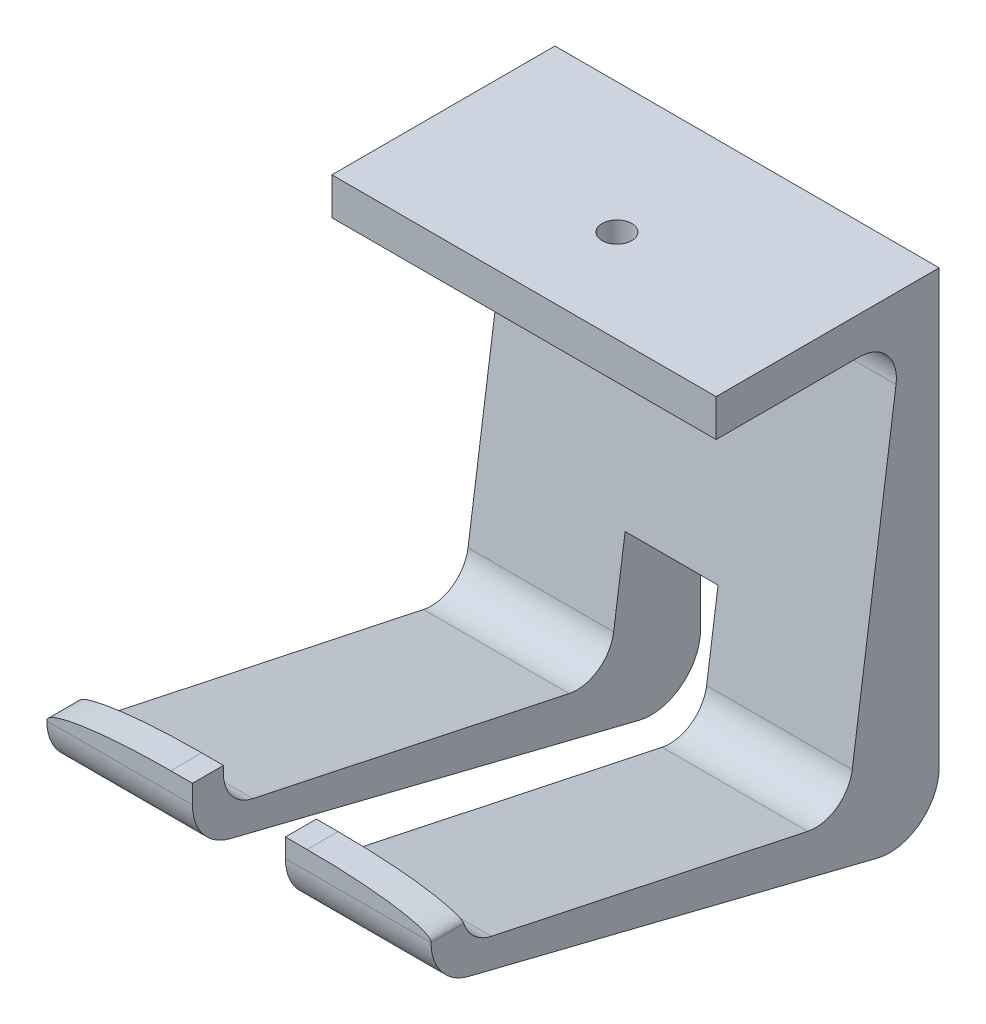
SolidWorks part; units mm, degrees
ref_plane "Front Plane" through (0, 0, 0) normal (0, 0, 1) x (1, 0, 0)
ref_plane "Top Plane" through (0, 0, 0) normal (0, 1, 0) x (1, 0, 0)
ref_plane "Right Plane" through (0, 0, 0) normal (1, 0, 0) x (0, 0, -1)
sketch "Sketch1" plane through (0, 0, 0) normal (1, 0, 0) x (0, 0, -1)
  line L0 (0, 0) -> (23.0978, 0)
  line L1 (29.0394, -6.835) -> (21.9739, -57.1088)
  line L2 (14.7848, -62.1426) -> (-36.2475, -51.2954)
  line L4 (0, 0) -> (0, 6)
  line L5 (0, 6) -> (36, 6)
  line L6 (36, 6) -> (36, -63.7605)
  line L7 (26.0646, -71.5228) -> (-39.9354, -55.0672)
  line L8 (-46, -47.3048) -> (-46, -44.2852)
  line L9 (-46, -44.2852) -> (-41, -44.2852)
  line L10 (-41, -44.2852) -> (-41, -45.4265)
  line L11 (0, 0) -> (0, -59) construction
  arc A0 (-36.2475, -51.2954) -> (-41, -45.4265) centre (-35, -45.4265) cw
  arc A1 (21.9739, -57.1088) -> (14.7848, -62.1426) centre (16.0323, -56.2737) cw
  arc A2 (23.0978, 0) -> (29.0394, -6.835) centre (23.0978, -6) cw
  arc A3 (-39.9354, -55.0672) -> (-46, -47.3048) centre (-38, -47.3048) cw
  arc A4 (36, -63.7605) -> (26.0646, -71.5228) centre (28, -63.7605) cw
  point P8 (45.1117, 0)
  point P12 (32.7633, -67.4398)
  point P14 (24.3841, 0)
  point P15 (18.7107, -64.6069)
  point P16 (0, 0)
  point P17 (24.5059, 0)
  point P18 (13.6637, -63.4514)
  point P19 (36, -73.0999)
  point P20 (-49.6643, -49.4999)
  point P21 (36, -76.3712)
  point P22 (-45.7564, -46.2852)
  point P23 (-46, -50.1234)
  point P26 (-41, -50.2852)
  point P31 (30, 0)
  point P36 (36, -74)
  dimension "D11" = 6
  dimension "D12" = 8
  dimension "D1" = 59
  dimension "D2" = 6
  dimension "D3" = 71
  dimension "D4" = 30
  dimension "D5" = 36
  dimension "D6" = 86
  dimension "82" = 82
  dimension "D7" = 76
  dimension "D8" = 5
  dimension "D9" = 80
  dimension "D10" = 6
extrude "Boss-Extrude1" add sketch "Sketch1" along normal mid plane 62
fillet "Fillet1" radius 3 1 edges at (-31, -44.2852, 43.5) second distance 20 first distance on face at (-31, -36.1034, 4.0702)
fillet "Fillet2" radius 3 1 edges at (31, -44.2852, 43.5) second distance 20 first distance on face at (31, -36.1034, 4.0702)
sketch "Sketch2" plane through (0, 0, 0) normal (0, 0, 1) x (1, 0, 0)
  line L0 (0, -44) -> (0, 0) construction
  line L1 (-7.5, -44) -> (7.5, -44)
  line L2 (-7.5, -44) -> (-7.5, -74)
  line L3 (-7.5, -74) -> (7.5, -74)
  line L4 (7.5, -44) -> (7.5, -74)
  dimension "D1" = 44
  dimension "D2" = 30
  dimension "D3" = 15
extrude "Cut-Extrude1" cut sketch "Sketch2" against normal through all both and the other way through all
sketch "Sketch4" plane through (0, 0, 0) normal (0, -1, 0) x (1, 0, 0)
  line L0 (0, 0) -> (0, -15) construction
  dimension "D1" = 15
hole_wizard "CSK for M4 Countersunk Flat Head Screw1" positions "3DSketch2" profile "Sketch5" countersink size "M4" standard "ISO"
sketch3d "3DSketch2"
  point P0 (0, 0, -15)
sketch "Sketch5" plane through (0, 0, -15) normal (1, 0, 0) x (0, 0, -1)
  line L0 (0, 0) -> (0, 16.6421)
  line L1 (0, 16.6421) -> (2.4, 15.2)
  line L2 (2.4, 15.2) -> (2.4, 2.3)
  line L3 (2.4, 2.3) -> (4.7, 0)
  line L5 (4.7, 0) -> (0, 0)
  line L6 (-2.4, 2.3) -> (-4.7, 0) construction
  line L10 (0, 16.6421) -> (-2.4, 15.2) construction
  line L11 (0, -6.35) -> (0, 107.95) construction
  dimension "Hole Dia." = 4.8
  dimension "Hole Depth" = 15.2
  dimension "Near C'Sink Dia." = 9.4
  dimension "Near C'Sink Angle" = 90
  dimension "Drill Angle" = 118
